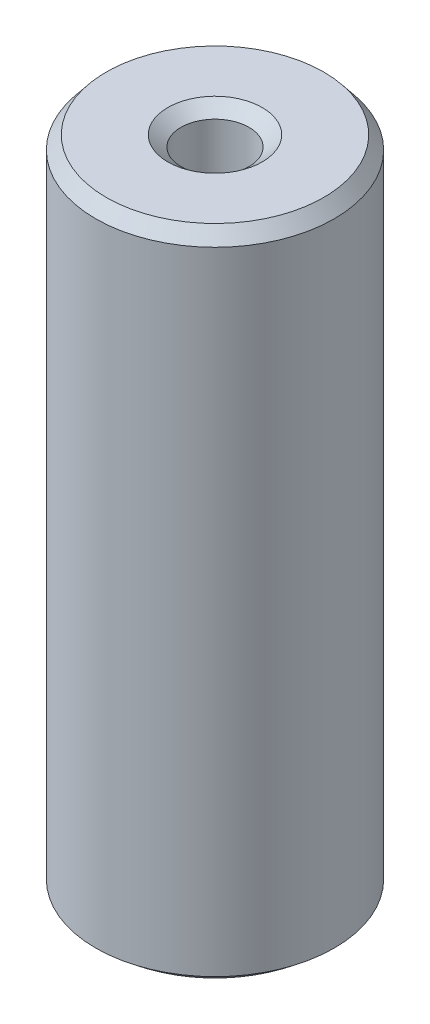
SolidWorks part; units mm, degrees
ref_plane "Front Plane" through (0, 0, 0) normal (0, 0, 1) x (1, 0, 0)
ref_plane "Top Plane" through (0, 0, 0) normal (0, 1, 0) x (1, 0, 0)
ref_plane "Right Plane" through (0, 0, 0) normal (1, 0, 0) x (0, 0, -1)
sketch "Sketch1" plane through (0, 0, 0) normal (0, 1, 0) x (1, 0, 0)
  circle A0 centre (0, 0) radius 5
  dimension "SLEEVE_OD" = 10
extrude "Boss-Extrude1" add sketch "Sketch1" along normal blind 27.472
sketch "Sketch2" plane through (0, 0, 0) normal (0, 1, 0) x (1, 0, 0)
  circle A0 centre (0, 0) radius 1.4266
  dimension "BORE_D" = 2.8531
extrude "Cut-Extrude1" cut sketch "Sketch2" along normal through all
chamfer "Chamfer1" distance 0.5517 angle 38.756 4 edges at (0, 27.472, 1.4266) (0, 0, 1.4266) (0, 0, 5) (0, 27.472, 5) first distance on face at (0, 27.472, 1.4266) first distance on face at (0, 0, 1.4266) first distance on face at (0, 27.472, 5)
